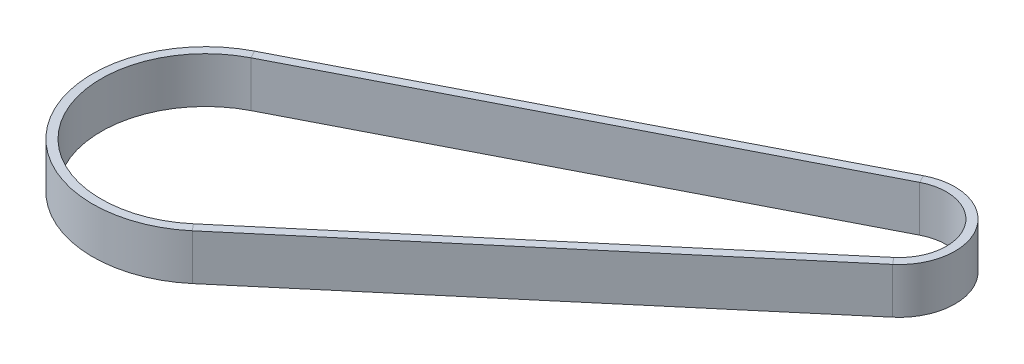
SolidWorks part; units mm, degrees
ref_plane "Front Plane" through (0, 0, 0) normal (0, 0, 1) x (1, 0, 0)
ref_plane "Top Plane" through (0, 0, 0) normal (0, 1, 0) x (1, 0, 0)
ref_plane "Right Plane" through (0, 0, 0) normal (1, 0, 0) x (0, 0, -1)
ref_axis "X" through (-88.99, 0, 0) along (1, 0, 0)
ref_axis "Y" through (0, 0, -88.99) along (0, 0, 1)
ref_axis "Z" through (0, 55, 0) along (0, -1, 0)
sketch "Sketch1" plane through (0, 0, 0) normal (0, 1, 0) x (1, 0, 0)
  line L0 (-26.2277, 550.8305) -> (128.4623, 630.0522)
  line L1 (148.2969, 600.2923) -> (15.6454, 488.0041)
  arc A0 (-26.2277, 550.8305) -> (15.6454, 488.0041) centre (-8.9061, 517.008) ccw
  arc A1 (148.2969, 600.2923) -> (128.4623, 630.0522) centre (136.6673, 614.031) ccw
  point P2 (-8.9061, 517.008)
  dimension "D1" = 38
  dimension "D2" = 18
ref_plane "Plane1" through (15.6454, 0, -488.0041) normal (-0.7633, 0, 0.6461) x (0.6461, 0, 0.7633)
sketch "Sketch2" plane through (15.6454, 0, -488.0041) normal (-0.7633, 0, 0.6461) x (0.6461, 0, 0.7633)
  line L0 (0, 0) -> (-35.5295, 0) construction
  line L1 (-1.5, 8) -> (1.5, 8)
  line L2 (-1.5, 8) -> (-1.5, -8)
  line L3 (-1.5, -8) -> (1.5, -8)
  line L4 (1.5, 8) -> (1.5, -8)
  line L5 (-1.5, 8) -> (1.5, -8) construction
  line L6 (-1.5, -8) -> (1.5, 8) construction
  point P0 (0, 0)
  dimension "D1" = 3
  dimension "D2" = 16
sweep "Sweep1" add profiles "Sketch2" path "Sketch1"
